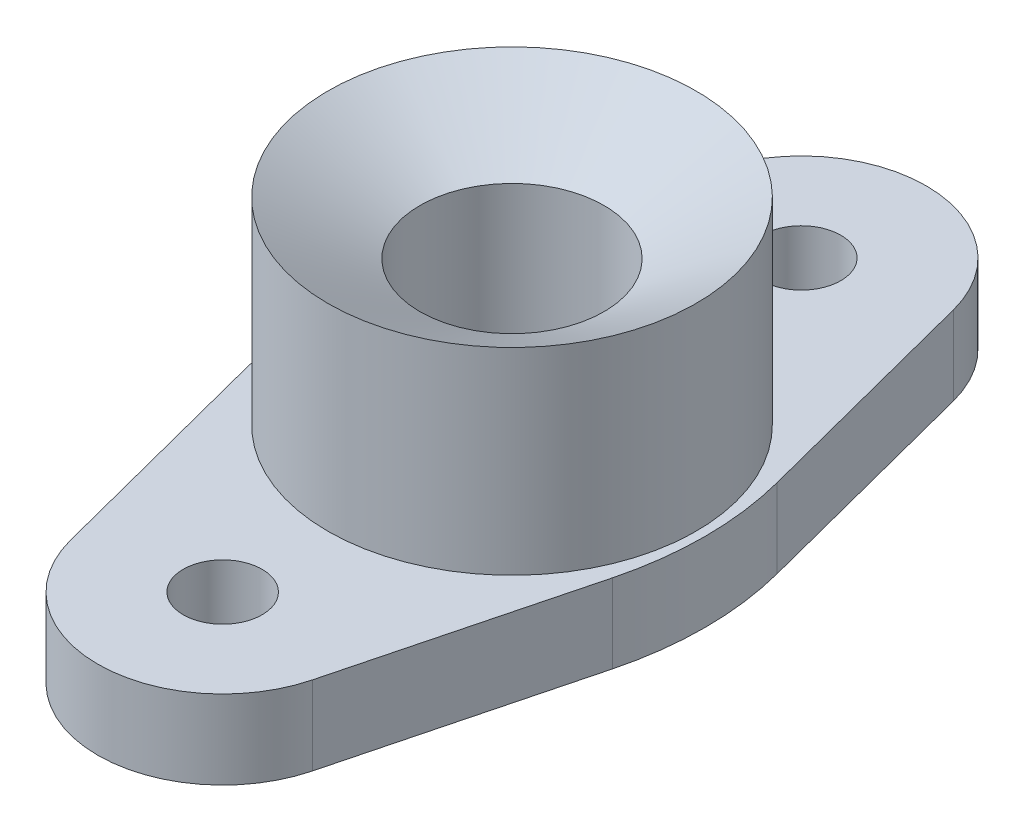
SolidWorks part; units mm, degrees
ref_plane "Front Plane" through (0, 0, 0) normal (0, 0, 1) x (1, 0, 0)
ref_plane "Top Plane" through (0, 0, 0) normal (0, 1, 0) x (1, 0, 0)
ref_plane "Right Plane" through (0, 0, 0) normal (1, 0, 0) x (0, 0, -1)
sketch "Sketch1" plane through (0, 0, 0) normal (0, 1, 0) x (1, 0, 0)
  line L0 (0, 44) -> (0, -44)
  line L1 (-18.3952, 48.7557) -> (-31, 0)
  line L2 (-31, 0) -> (-18.3952, -48.7557)
  line L3 (18.3952, -48.7557) -> (31, 0)
  line L4 (18.3952, 48.7557) -> (31, 0)
  circle A1 centre (0, 44) radius 19
  circle A2 centre (0, -44) radius 19
  circle A3 centre (0, 44) radius 6
  circle A4 centre (0, -44) radius 6
  circle A5 centre (0, 0) radius 14
  point P5 (0, 0)
  dimension "D1" = 62
  dimension "D3" = 38
  dimension "D4" = 12
  dimension "D5" = 28
  dimension "D2" = 88
  dimension "D6" = 31
extrude "Boss-Extrude1" add sketch "Sketch1" along normal mid plane 12 contours A4 A2 | A2 L2 | A5 L0 A1 A2 | A2 L3 | A1 L4 | A5 L0 A2 A1 | A3 A1 | A1 L1 | L0 A2 | A2 L0 | A1 L0 | L0 A1 region at (-14.5977, 0, -32.6963) region at (16.4646, 0, 0) region at (-16.4646, 0, 0) region at (5.9418, 0, 0) region at (-5.9418, 0, 0) region at (13.055, 0, 30.945)
fillet "Fillet1" radius 50 2 edges at (-31, 0, 0) (31, 0, 0)
sketch "Sketch4" plane through (0, 6, 0) normal (0, 1, 0) x (1, 0, 0)
  circle A0 centre (0, 0) radius 28
  circle A1 centre (0, 0) radius 14
  dimension "D1" = 56
  dimension "D2" = 28
extrude "Boss-Extrude3" add sketch "Sketch4" along normal blind 30
extrude "Cut-Extrude1" cut sketch "Sketch4<2>" against normal through all contours A1 region at (0, 6, 0)
sketch "Sketch4<2>" plane through (0, 6, 0) normal (0, 1, 0) x (1, 0, 0) same geometry as "Sketch4"
sketch "Sketch5" plane through (0, 36, 0) normal (0, 1, 0) x (1, 0, 0)
  circle A0 centre (0, 0) radius 28 construction
  circle A1 centre (0, 0) radius 28
extrude "Cut-Extrude3" cut sketch "Sketch5" against normal through all draft 60
